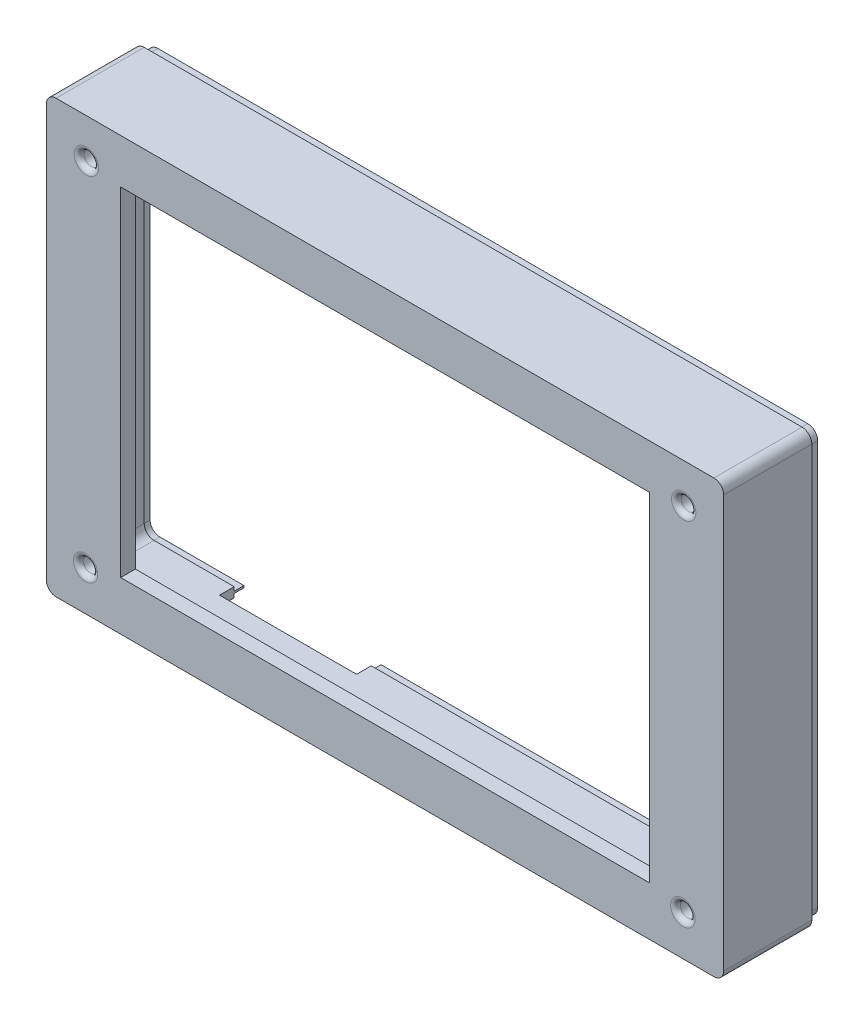
SolidWorks part; units mm, degrees
ref_plane "Front Plane" through (0, 0, 0) normal (0, 0, 1) x (1, 0, 0)
ref_plane "Top Plane" through (0, 0, 0) normal (0, 1, 0) x (1, 0, 0)
ref_plane "Right Plane" through (0, 0, 0) normal (1, 0, 0) x (0, 0, -1)
sketch "Szkic2" plane through (0, 0, 0) normal (0, 0, 1) x (1, 0, 0)
  line L0 (-320.9886, 303.116) -> (-320.9886, 226.8952)
  line L1 (-320.9886, 226.8952) -> (-190.611, 226.8952)
  line L2 (-190.611, 226.8952) -> (-190.611, 307.1276)
  line L3 (-190.611, 307.1276) -> (-320.9886, 307.1276)
  line L4 (-320.9886, 307.1276) -> (-320.9886, 303.116)
  line L5 (-255.7997, 302.0115) -> (-255.7997, 276.2295)
  line L6 (-309.7997, 232.9127) -> (-201.7997, 232.9127)
  line L7 (-309.7997, 232.9127) -> (-309.7997, 302.0115)
  line L8 (-309.7997, 302.0115) -> (-201.7997, 302.0115)
  line L9 (-201.7997, 232.9127) -> (-201.7997, 302.0115)
  line L10 (-324.9886, 311.1276) -> (-186.611, 311.1276)
  line L11 (-324.9886, 311.1276) -> (-324.9886, 222.8952)
  line L12 (-324.9886, 222.8952) -> (-186.611, 222.8952)
  line L13 (-186.611, 311.1276) -> (-186.611, 222.8952)
  circle A0 centre (-316.8147, 303.116) radius 1.4929
  circle A1 centre (-316.9771, 231.116) radius 1.4823
  circle A2 centre (-194.9471, 231.116) radius 1.5071
  circle A4 centre (-194.7847, 303.116) radius 1.4929
  point P26 (-255.7997, 267.0115)
  dimension "D5" = 122.03
  dimension "D6" = 122.03
  dimension "D7" = 72
  dimension "D8" = 72.0002
  dimension "D1" = 4
  dimension "D2" = 4
  dimension "D3" = 4
  dimension "D4" = 4
  dimension "D9" = 54
  dimension "D10" = 35
extrude "Dodanie-wyciągnięcie1" add sketch "Szkic2" along normal blind 3 contours L3 L4 L0 L1 L2 A2 A1 A0 L9 L6 L7 L8 | L13 L10 L11 L12 L4 L3 L2 L1 L0 region at (-319.4577, 305.1218, 0) region at (-255.7998, 309.4864, 0)
sketch "Szkic3" plane through (0, 0, 0) normal (0, 0, -1) x (-1, 0, 0)
  line L1 (186.611, 311.1276) -> (324.9886, 311.1276)
  line L2 (186.611, 311.1276) -> (186.611, 222.8952)
  line L3 (186.611, 222.8952) -> (324.9886, 222.8952)
  line L4 (324.9886, 311.1276) -> (324.9886, 222.8952)
extrude "Wyciągnięcie-cienka ścianka1" add sketch "Szkic3" along normal blind 15 thin thin type one direction reverse wall 2
fillet "Zaokrąglenie1" radius 1 4 edges at (-193.2918, 303.116, 3) (-193.44, 231.116, 3) (-315.4948, 231.116, 3) (-315.3218, 303.116, 3)
sketch "Szkic4" plane through (0, 0, 0) normal (0, 0, -1) x (-1, 0, 0)
  circle A0 centre (194.7847, 303.116) radius 2.4929
  circle A1 centre (194.9471, 231.116) radius 2.5071
  circle A2 centre (316.9771, 231.116) radius 2.4823
  circle A3 centre (316.8147, 303.116) radius 2.4929
  circle A4 centre (316.8147, 303.116) radius 1.4929 construction
  circle A5 centre (316.9771, 231.116) radius 1.4823 construction
  circle A6 centre (194.7847, 303.116) radius 1.4929 construction
  circle A7 centre (194.9471, 231.116) radius 1.5071 construction
  circle A8 centre (316.8147, 303.116) radius 1.4929
  circle A9 centre (316.9771, 231.116) radius 1.4823
  circle A10 centre (194.9471, 231.116) radius 1.5071
  circle A11 centre (194.7847, 303.116) radius 1.4929
  dimension "D1" = 1
  dimension "D2" = 1
  dimension "D3" = 1
  dimension "D4" = 1
extrude "Dodanie-wyciągnięcie2" add sketch "Szkic4" along normal blind 1
fillet "Zaokrąglenie2" radius 1 4 edges at (-192.44, 231.116, 0) (-314.4948, 231.116, 0) (-314.3218, 303.116, 0) (-192.2918, 303.116, 0)
sketch "Szkic5" plane through (0, 0, -15) normal (0, 0, -1) x (-1, 0, 0)
  line L0 (186.611, 222.8952) -> (324.9886, 222.8952) construction
  line L1 (187.611, 310.1276) -> (323.9886, 310.1276)
  line L2 (187.611, 310.1276) -> (187.611, 223.8952)
  line L3 (187.611, 223.8952) -> (323.9886, 223.8952)
  line L4 (323.9886, 310.1276) -> (323.9886, 223.8952)
  line L5 (186.611, 311.1276) -> (186.611, 222.8952) construction
  line L6 (324.9886, 311.1276) -> (186.611, 311.1276) construction
  line L7 (324.9886, 222.8952) -> (324.9886, 311.1276) construction
  dimension "D1" = 1
  dimension "D2" = 1
  dimension "D3" = 1
  dimension "D4" = 1
extrude "Wyciągnięcie-cienka ścianka2" add sketch "Szkic5" along normal blind 2 thin thin type mid plane wall 0.4
fillet "Zaokrąglenie3" radius 2 16 edges at (-187.411, 310.3276, -16) (-186.611, 311.1276, -6) (-187.811, 309.9276, -16) (-188.611, 309.1276, -7.5) (-187.811, 224.0952, -16) (-188.611, 224.8952, -7.5) (-187.411, 223.6952, -16) (-186.611, 222.8952, -6) (-324.9886, 222.8952, -6) (-324.1886, 223.6952, -16) (-323.7886, 224.0952, -16) (-322.9886, 224.8952, -7.5) (-323.7886, 309.9276, -16) (-324.1886, 310.3276, -16) (-322.9886, 309.1276, -7.5) (-324.9886, 311.1276, -6)
sketch "Szkic6" plane through (0, 0, 0) normal (0, 0, -1) x (-1, 0, 0)
  line L1 (276.611, 224.9127) -> (304.611, 224.9127)
  line L2 (276.611, 224.9127) -> (276.611, 217.5809)
  line L3 (276.611, 217.5809) -> (304.611, 217.5809)
  line L4 (304.611, 224.9127) -> (304.611, 217.5809)
  line L5 (188.611, 307.1276) -> (188.611, 226.8952) construction
  line L6 (309.7997, 232.9127) -> (201.7997, 232.9127) construction
  dimension "D1" = 88
  dimension "D2" = 28
  dimension "D3" = 8
extrude "Wytnij-wyciągnięcie1" cut sketch "Szkic6" along normal through all from offset 12
